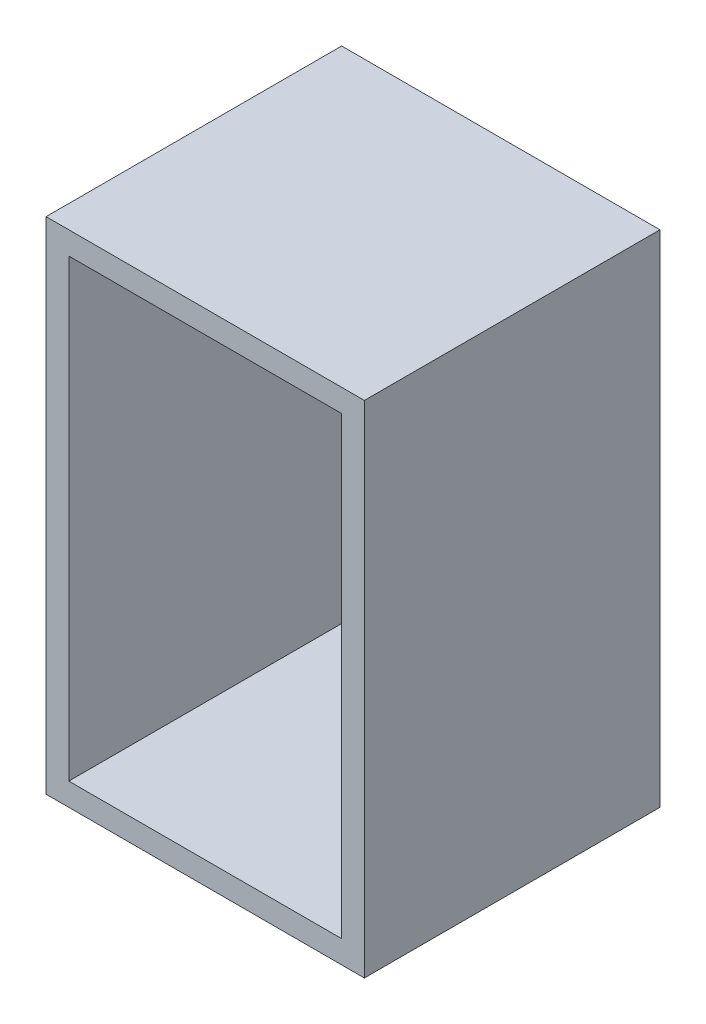
SolidWorks part; units mm, degrees
ref_plane "Front Plane" through (0, 0, 0) normal (0, 0, 1) x (1, 0, 0)
ref_plane "Top Plane" through (0, 0, 0) normal (0, 1, 0) x (1, 0, 0)
ref_plane "Right Plane" through (0, 0, 0) normal (1, 0, 0) x (0, 0, -1)
sketch "Sketch2" plane through (0, 0, 0) normal (0, 0, 1) x (1, 0, 0)
  line L1 (-177.8, 279.4) -> (177.8, 279.4)
  line L2 (-177.8, 279.4) -> (-177.8, -279.4)
  line L3 (-177.8, -279.4) -> (177.8, -279.4)
  line L4 (177.8, 279.4) -> (177.8, -279.4)
  point P4 (-177.8, 0)
  point P6 (0, 279.4)
  dimension "D1" = 355.6
  dimension "D2" = 558.8
extrude "Boss-Extrude1" add sketch "Sketch2" along normal blind 25.4
sketch "Sketch3" plane through (0, 0, 25.4) normal (0, 0, 1) x (1, 0, 0)
  line L0 (-177.8, 279.4) -> (177.8, 279.4)
  line L1 (177.8, 279.4) -> (177.8, -279.4)
  line L2 (177.8, -279.4) -> (-177.8, -279.4)
  line L3 (-177.8, -279.4) -> (-177.8, 279.4)
  line L4 (-152.4, 254) -> (152.4, 254)
  line L5 (152.4, 254) -> (152.4, -254)
  line L6 (152.4, -254) -> (-152.4, -254)
  line L7 (-152.4, -254) -> (-152.4, 254)
  dimension "D1" = 25.4
  dimension "D2" = 25.4
  dimension "D3" = 25.4
  dimension "D4" = 25.4
extrude "Boss-Extrude2" add sketch "Sketch3" along normal blind 304.8
